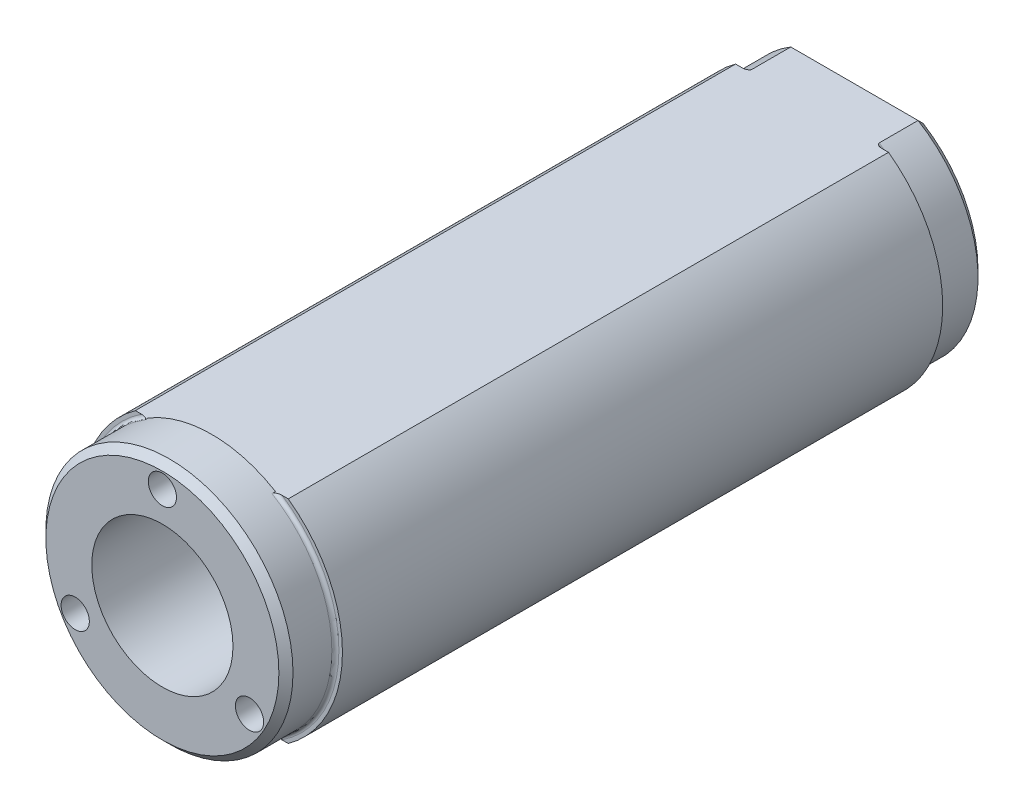
SolidWorks part; units mm, degrees
material "1.0503 (C45)"
ref_plane "Front Plane" through (0, 0, 0) normal (0, 0, 1) x (1, 0, 0)
ref_plane "Top Plane" through (0, 0, 0) normal (0, 1, 0) x (1, 0, 0)
ref_plane "Right Plane" through (0, 0, 0) normal (1, 0, 0) x (0, 0, -1)
sketch "Sketch1" plane through (0, 0, 0) normal (0, 0, 1) x (1, 0, 0)
  line L0 (0, 24.7328) -> (0, -23.7417) construction
  line L1 (-10.8282, 15) -> (10.8282, 15)
  line L2 (-10.8282, -15) -> (10.8282, -15)
  circle A0 centre (0, 0) radius 10
  circle A1 centre (0, 0) radius 17.5
  circle A2 centre (0, 0) radius 18.5
  point P6 (0, 15)
  point P7 (0, -15)
  dimension "D1" = 15
  dimension "D2" = 37
  dimension "D3" = 35
  dimension "D5" = 15
  dimension "D4" = 20
extrude "Boss-Extrude1" add sketch "Sketch1" along normal blind 49.5 and the other way blind 49.5 contours L1 L0 A0 L2 A1 | L0 L1 A1 L2 A0 region at (4.5069, 14.6527, 0) region at (-0.3473, 12.5, 0)
extrude "Boss-Extrude2" add sketch "Sketch1<23>" along normal blind 42.5 and the other way blind 42.5 contours L2 A2 L1 A1 | L1 A2 L2 A1 region at (-9.921, 14.6854, 0) region at (16.1906, 8.2807, 0)
sketch "Sketch1<23>" plane through (0, 0, 0) normal (0, 0, 1) x (1, 0, 0) same geometry as "Sketch1"
ref_plane "Plane1" through (0, 0, 49.5) normal (0, 0, 1) x (1, 0, 0)
sketch "Sketch5" plane through (0, 0, 49.5) normal (0, 0, 1) x (1, 0, 0)
  line L0 (0, 24.7328) -> (0, -23.7417) construction
  line L1 (-10.8282, 15) -> (10.8282, 15)
  line L2 (-10.8282, -15) -> (10.8282, -15)
  circle A0 centre (0, 0) radius 10
  circle A1 centre (0, 0) radius 17.5
  circle A2 centre (0, 0) radius 18.5
  point P6 (0, 15)
  point P7 (0, -15)
  dimension "D1" = 15
  dimension "D2" = 37
  dimension "D3" = 35
  dimension "D5" = 15
  dimension "D4" = 20
extrude "Boss-Extrude3" add sketch "Sketch5" against normal blind 7 contours L0 L1 A1 L2 A0 | L1 L0 A0 L2 A1 | L0 A1 L1 | A1 L0 L1 | L2 L0 A1 | L0 L2 A1 region at (3.4149, 16.0064, 49.5) region at (-3.4149, 16.0064, 49.5) region at (4.5069, 14.6527, 49.5) region at (-0.3473, 12.5, 49.5) region at (-3.4149, -16.0064, 49.5) region at (3.4149, -16.0064, 49.5)
sketch "Sketch6" plane through (0, 0, 49.5) normal (0, 0, 1) x (1, 0, 0)
  line L0 (0, 0) -> (0, 22.9778) construction
  circle A0 centre (0, 14.25) radius 2
  circle A1 centre (12.3409, -7.125) radius 2
  circle A2 centre (-12.3409, -7.125) radius 2
  point P3 (0, 14.25)
  point P13 (0, 0)
  dimension "D2" = 4
  dimension "D1" = 14.25
  dimension "D3" = 3
extrude "Cut-Extrude1" cut sketch "Sketch6" against normal blind 5
ref_plane "Plane2" through (0, 0, -46.5) normal (0, 0, -1) x (-1, 0, 0)
hole_wizard "M3 Tapped Hole1" positions "Sketch8" profile "Sketch9" tap size "M3" standard "ISO"
sketch "Sketch8" plane through (0, -15, 0) normal (0, -1, 0) x (-1, 0, 0)
  point P0 (0, 0)
sketch "Sketch9" plane through (0, -15, 0) normal (1, 0, 0) x (0, 0, -1)
  line L0 (0, 0) -> (0, 8.2511)
  line L1 (0, 8.2511) -> (1.25, 7.5)
  line L2 (1.25, 7.5) -> (1.25, 0.275)
  line L3 (1.25, 0.275) -> (1.525, 0)
  line L5 (1.525, 0) -> (0, 0)
  line L6 (-1.25, 0.275) -> (-1.525, 0) construction
  line L10 (0, 8.2511) -> (-1.25, 7.5) construction
  line L11 (0, -6.35) -> (0, 107.95) construction
  dimension "Tap Drill Dia." = 2.5
  dimension "Tap Drill Depth" = 7.5
  dimension "Near C'Sink Dia." = 3.05
  dimension "Near C'Sink Angle" = 90
  dimension "Drill Angle" = 118
fillet "Fillet1" radius 0.5 4 edges at (-17.5, 0, -42.5) (17.5, 0, -42.5) (17.5, 0, 42.5) (-17.5, 0, 42.5)
chamfer "Chamfer1" distance 1 angle 45 3 edges at (17.5, 0, 49.5) (17.5, 0, -49.5) (-17.5, 0, -49.5)
chamfer "Chamfer2" distance 1 angle 45 2 edges at (0, -15, -49.5) (0, 15, -49.5)
